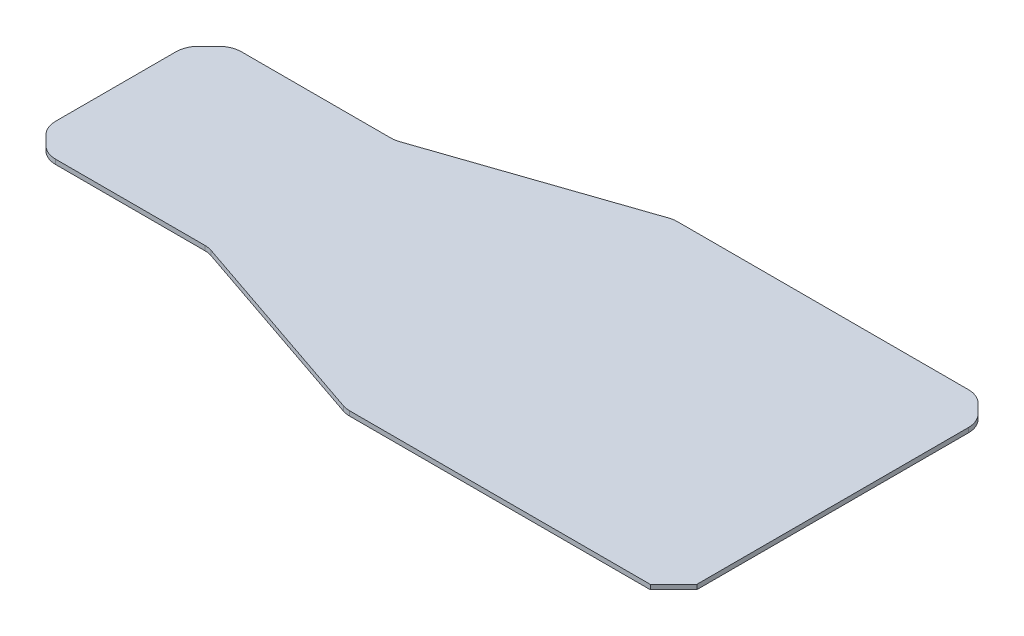
SolidWorks part; units mm, degrees
ref_plane "Front Plane" through (0, 0, 0) normal (0, 0, 1) x (1, 0, 0)
ref_plane "Top Plane" through (0, 0, 0) normal (0, 1, 0) x (1, 0, 0)
ref_plane "Right Plane" through (0, 0, 0) normal (1, 0, 0) x (0, 0, -1)
sketch "Sketch1" plane through (0, 0, 0) normal (0, 1, 0) x (1, 0, 0)
  line L0 (0, 0) -> (200, 0) construction
  line L1 (40, 40) -> (129.5, 70.5)
  line L2 (129.5, 70.5) -> (270.5, 70.5)
  line L3 (129.5, 70.5) -> (129.5, -70.5) construction
  line L4 (129.5, -70.5) -> (270.5, -70.5)
  line L5 (270.5, 70.5) -> (270.5, -70.5)
  line L6 (129.5, 70.5) -> (270.5, -70.5) construction
  line L7 (129.5, -70.5) -> (270.5, 70.5) construction
  line L8 (-40, 40) -> (40, 40)
  line L9 (-40, 40) -> (-40, -40)
  line L10 (-40, -40) -> (40, -40)
  line L11 (40, 40) -> (40, -40) construction
  line L12 (-40, 40) -> (40, -40) construction
  line L13 (-40, -40) -> (40, 40) construction
  line L14 (40, -40) -> (129.5, -70.5)
  dimension "D1" = 200
  dimension "D2" = 141
  dimension "D3" = 80
extrude "Boss-Extrude1" add sketch "Sketch1" along normal blind 2
chamfer "Chamfer1" distance 10 angle 45 4 edges at (-40, 1, -40) (270.5, 1, -70.5) (270.5, 1, 70.5) (-40, 1, 40)
fillet "Fillet1" radius 10 10 edges at (-30, 1, 40) (-40, 1, 30) (-30, 1, -40) (-40, 1, -30) (270.5, 1, -60.5) (260.5, 1, -70.5) (40, 1, 40) (129.5, 1, 70.5) (40, 1, -40) (129.5, 1, -70.5)
equation "\"Elevator Diameter\"= 135mm"
equation "\"Plate Thickness\"= 2mm"
equation "\"Pivot to Pivot Distance\"= 200mm"
equation "\"D1@Sketch1\"=\"Pivot to Pivot Distance\""
equation "\"Extra Spacing\"= 3mm"
equation "\"D2@Sketch1\"=\"Elevator Diameter\"+\"Extra Spacing\"*2"
equation "\"Servo Size\"= 40mm"
equation "\"D1@Boss-Extrude1\"=\"Plate Thickness\""
